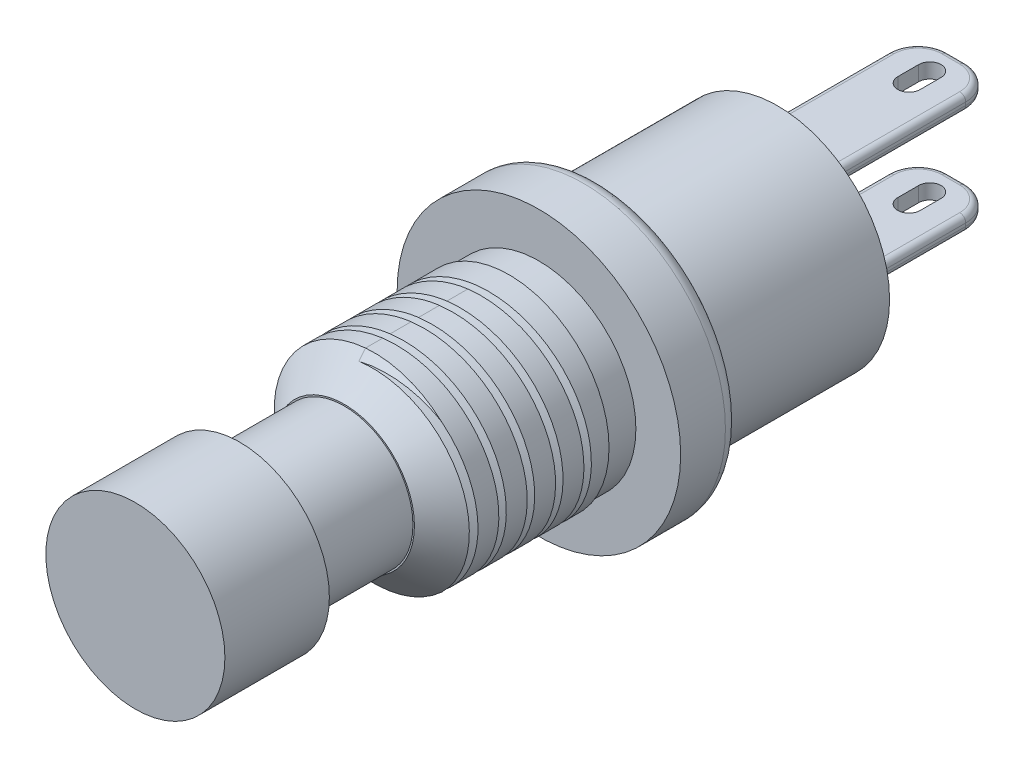
SolidWorks part; units mm, degrees
ref_plane "Front Plane" through (0, 0, 0) normal (0, 0, 1) x (1, 0, 0)
ref_plane "Top Plane" through (0, 0, 0) normal (0, 1, 0) x (1, 0, 0)
ref_plane "Right Plane" through (0, 0, 0) normal (1, 0, 0) x (0, 0, -1)
sketch "Sketch1" plane through (0, 0, 0) normal (0, 0, 1) x (1, 0, 0)
  circle A0 centre (0, 0) radius 3.75
  dimension "D1" = 7.5
extrude "Boss-Extrude1" add sketch "Sketch1" along normal blind 6
sketch "Sketch2" plane through (0, 0, 6) normal (0, 0, 1) x (1, 0, 0)
  circle A0 centre (0, 0) radius 4.75
  dimension "D1" = 9.5
extrude "Boss-Extrude2" add sketch "Sketch2" along normal blind 2
fillet "Fillet1" radius 0.5 1 edges at (4.75, 0, 6)
sketch "Sketch3" plane through (0, 0, 8) normal (0, 0, 1) x (1, 0, 0)
  circle A0 centre (0, 0) radius 3.25
  dimension "D1" = 6.5
extrude "Boss-Extrude3" add sketch "Sketch3" along normal blind 1
sketch "Sketch4" plane through (0, 0, 9) normal (0, 0, 1) x (1, 0, 0)
  circle A0 centre (0, 0) radius 3.35
  dimension "D1" = 6.7
extrude "Boss-Extrude4" add sketch "Sketch4" along normal blind 5.52
chamfer "Chamfer1" distance 1 angle 45 1 edges at (3.35, 0, 14.52)
sketch "Sketch5" plane through (0, 0, 14.52) normal (0, 0, 1) x (1, 0, 0)
  circle A0 centre (0, 0) radius 2.3
  dimension "D1" = 4.6
extrude "Boss-Extrude5" add sketch "Sketch5" along normal blind 3.5
sketch "Sketch6" plane through (0, 0, 18.02) normal (0, 0, 1) x (1, 0, 0)
  circle A0 centre (0, 0) radius 3
  dimension "D1" = 6
extrude "Boss-Extrude6" add sketch "Sketch6" along normal blind 3.5
sketch "Sketch7" plane through (0, 0, 0) normal (0, 0, -1) x (-1, 0, 0)
  line L1 (-1.3, 2.2093) -> (1.3, 2.2093)
  line L2 (-1.3, 2.2093) -> (-1.3, 1.7093)
  line L3 (-1.3, 1.7093) -> (1.3, 1.7093)
  line L4 (1.3, 2.2093) -> (1.3, 1.7093)
  line L5 (-1.3, 2.2093) -> (1.3, 1.7093) construction
  line L6 (-1.3, 1.7093) -> (1.3, 2.2093) construction
  line L7 (-1.3, -1.3001) -> (1.3, -1.3001)
  line L8 (-1.3, -1.3001) -> (-1.3, -1.8001)
  line L9 (-1.3, -1.8001) -> (1.3, -1.8001)
  line L10 (1.3, -1.3001) -> (1.3, -1.8001)
  line L11 (-1.3, -1.3001) -> (1.3, -1.8001) construction
  line L12 (-1.3, -1.8001) -> (1.3, -1.3001) construction
  point P0 (0, 1.9593)
  point P5 (0, -1.5501)
  dimension "D1" = 2.6
  dimension "D2" = 2.6
  dimension "D3" = 0.5
  dimension "D4" = 0.5
  dimension "D5" = 0
  dimension "D6" = 0
extrude "Boss-Extrude7" add sketch "Sketch7" along normal blind 6
fillet "Fillet4" radius 1 4 edges at (1.3, 1.9593, -6) (-1.3, 1.9593, -6) (-1.3, -1.5501, -6) (1.3, -1.5501, -6)
sketch "Sketch8" plane through (0, -1.8001, 0) normal (0, -1, 0) x (1, 0, 0)
  line L0 (0, -4.4) -> (0, -5.1) construction
  line L1 (0.375, -4.4) -> (0.375, -5.1)
  line L2 (-0.375, -4.4) -> (-0.375, -5.1)
  line L3 (0.3, -6) -> (-0.3, -6) construction
  arc A0 (0.375, -4.4) -> (-0.375, -4.4) centre (0, -4.4) ccw
  arc A1 (-0.375, -5.1) -> (0.375, -5.1) centre (0, -5.1) ccw
  point P3 (0, -4.75)
  dimension "D1" = 0.7
  dimension "D2" = 0.75
  dimension "D3" = 0.9
extrude "Cut-Extrude1" cut sketch "Sketch8" against normal blind 6
fillet "Fillet5" radius 0.2 20 edges at (-1.3, 2.2093, -2.5) (-1.0071, 2.2093, -5.7071) (0, 2.2093, -6) (1.0071, 2.2093, -5.7071) (-1.3, -1.3001, -2.5) (-1.0071, -1.3001, -5.7071) (0, -1.3001, -6) (1.0071, -1.3001, -5.7071) (-1.3, -1.8001, -2.5) (-1.0071, -1.8001, -5.7071) (0, -1.8001, -6) (1.0071, -1.8001, -5.7071) (1.3, 1.7093, -2.5) (1.0071, 1.7093, -5.7071) (0, 1.7093, -6) (-1.0071, 1.7093, -5.7071) (1.3, 2.2093, -2.5) (1.3, -1.3001, -2.5) (1.3, -1.8001, -2.5) (-1.3, 1.7093, -2.5)
sketch "Sketch9" plane through (0, 0, 0) normal (0, 1, 0) x (1, 0, 0)
  line L0 (3.1, -13.52) -> (4.1, -13.02)
  line L1 (3.35, -13.52) -> (-3.35, -13.52) construction
  line L2 (4.1, -13.02) -> (4.1, -14.02)
  line L3 (4.1, -14.02) -> (3.1, -13.52)
  line L4 (3.1, -13.52) -> (4.367, -13.52) construction
  line L5 (3.35, -13.52) -> (3.35, -9) construction
  dimension "D1" = 1
  dimension "D2" = 0.5
  dimension "D3" = 1
  dimension "D4" = 0.25
sketch "Sketch10" plane through (0, 0, 14.52) normal (0, 0, 1) x (1, 0, 0)
  circle A0 centre (0, 0) radius 3.35
curve "Helix/Spiral1" pitch 0.95 height 5.4625 radius 3.35 centre (0, 0, 14.52) axis (0, 0, -1) start towards (-1, 0, 0)
sweep "Cut-Sweep1" cut profiles "Sketch9" path "Helix/Spiral1"
